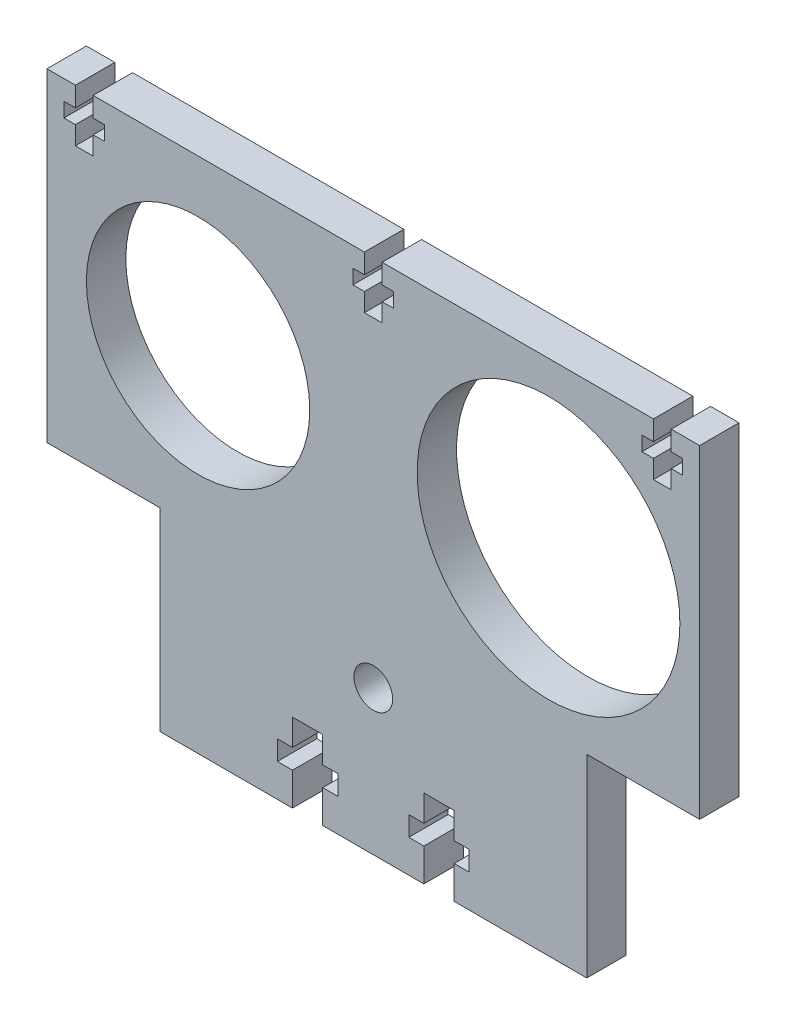
SolidWorks part; units mm, degrees
material "ABS"
ref_plane "Front Plane" through (0, 0, 0) normal (0, 0, 1) x (1, 0, 0)
ref_plane "Top Plane" through (0, 0, 0) normal (0, 1, 0) x (1, 0, 0)
ref_plane "Right Plane" through (0, 0, 0) normal (1, 0, 0) x (0, 0, -1)
sketch "Sketch1" plane through (0, 0, 0) normal (0, 0, 1) x (1, 0, 0)
  line L0 (0, 0) -> (-26.6757, 31.7908) construction
  line L1 (0, 0) -> (0, 56.7908) construction
  line L2 (-32.5, 7.5) -> (-32.5, -22)
  line L3 (-32.5, -22) -> (32.5, -22)
  line L4 (32.5, 7.5) -> (49.6757, 7.5)
  line L5 (0, 0) -> (0, -22) construction
  line L6 (49.6757, 7.5) -> (49.6757, 56.7908)
  line L7 (0, 0) -> (26.6757, 31.7908) construction
  line L10 (-32.5, 7.5) -> (-49.6757, 7.5)
  line L11 (-49.6757, 7.5) -> (-49.6757, 56.7908)
  line L12 (-49.6757, 56.7908) -> (49.6757, 56.7908)
  line L13 (32.5, 7.5) -> (32.5, -22)
  circle A0 centre (0, 0) radius 2.95
  circle A1 centre (-26.6757, 31.7908) radius 17
  circle A2 centre (26.6757, 31.7908) radius 20
  point P16 (0, 56.7908)
  dimension "D1" = 5.9
  dimension "D9" = 34
  dimension "D10" = 40
  dimension "D2" = 41.5
  dimension "D4" = 40
  dimension "D5" = 22
  dimension "D6" = 65
  dimension "D7" = 29.5
  dimension "D8" = 23
  dimension "D3" = 25
  dimension "D11" = 40
extrude "Boss-Extrude1" add sketch "Sketch1" along normal blind 6
sketch "Sketch3" plane through (0, 0, 6) normal (0, 0, 1) x (1, 0, 0)
  line L0 (-32.5, -22) -> (32.5, -22) construction
  line L1 (-12.3, -22) -> (-7.7, -22)
  line L2 (-12.3, -22) -> (-12.3, -17)
  line L3 (-12.3, -10) -> (-7.7, -10)
  line L4 (-7.7, -22) -> (-7.7, -17)
  line L5 (0, 0) -> (0, -22) construction
  line L6 (-7.7, -14) -> (-5.4, -14)
  line L7 (-14.6, -14) -> (-12.3, -14)
  line L8 (-14.6, -14) -> (-14.6, -17)
  line L9 (-14.6, -17) -> (-12.3, -17)
  line L10 (-5.4, -14) -> (-5.4, -17)
  line L11 (-12.3, -14) -> (-12.3, -10)
  line L12 (-7.7, -17) -> (-5.4, -17)
  line L13 (-7.7, -14) -> (-7.7, -10)
  line L14 (7.7, -14) -> (7.7, -10)
  line L15 (7.7, -17) -> (5.4, -17)
  line L16 (12.3, -14) -> (12.3, -10)
  line L17 (5.4, -14) -> (5.4, -17)
  line L18 (14.6, -17) -> (12.3, -17)
  line L19 (14.6, -14) -> (14.6, -17)
  line L20 (14.6, -14) -> (12.3, -14)
  line L21 (7.7, -14) -> (5.4, -14)
  line L22 (7.7, -22) -> (7.7, -17)
  line L23 (12.3, -10) -> (7.7, -10)
  line L24 (12.3, -22) -> (12.3, -17)
  line L25 (12.3, -22) -> (7.7, -22)
  point P6 (-10, -10)
  point P18 (-13.45, -17)
  dimension "D1" = 4.6
  dimension "D2" = 10
  dimension "D3" = 12
  dimension "D4" = 9.2
  dimension "D5" = 3
  dimension "D6" = 5
extrude "Cut-Extrude2" cut sketch "Sketch3" against normal through all
sketch "Sketch4" plane through (0, 0, 6) normal (0, 0, 1) x (1, 0, 0)
  line L0 (42.65, 56.7908) -> (42.65, 53.7908)
  line L1 (49.6757, 56.7908) -> (-49.6757, 56.7908) construction
  line L2 (42.65, 53.7908) -> (40.9, 53.7908)
  line L3 (40.9, 53.7908) -> (40.9, 51.5908)
  line L4 (40.9, 51.5908) -> (42.65, 51.5908)
  line L5 (42.65, 51.5908) -> (42.65, 48.7908)
  line L6 (42.65, 48.7908) -> (45.35, 48.7908)
  line L7 (45.35, 48.7908) -> (45.35, 51.5908)
  line L8 (45.35, 51.5908) -> (47.1, 51.5908)
  line L9 (47.1, 51.5908) -> (47.1, 53.7908)
  line L10 (47.1, 53.7908) -> (45.35, 53.7908)
  line L11 (45.35, 53.7908) -> (45.35, 56.7908)
  line L12 (45.35, 56.7908) -> (42.65, 56.7908)
  line L13 (0, 0) -> (0, 56.7908) construction
  line L14 (-45.35, 56.7908) -> (-42.65, 56.7908)
  line L15 (-45.35, 53.7908) -> (-45.35, 56.7908)
  line L16 (-47.1, 53.7908) -> (-45.35, 53.7908)
  line L17 (-47.1, 51.5908) -> (-47.1, 53.7908)
  line L18 (-45.35, 51.5908) -> (-47.1, 51.5908)
  line L19 (-45.35, 48.7908) -> (-45.35, 51.5908)
  line L20 (-42.65, 48.7908) -> (-45.35, 48.7908)
  line L21 (-42.65, 51.5908) -> (-42.65, 48.7908)
  line L22 (-40.9, 51.5908) -> (-42.65, 51.5908)
  line L23 (-40.9, 53.7908) -> (-40.9, 51.5908)
  line L24 (-42.65, 53.7908) -> (-40.9, 53.7908)
  line L25 (-42.65, 56.7908) -> (-42.65, 53.7908)
  line L26 (-1.35, 56.7908) -> (1.35, 56.7908)
  line L27 (1.35, 56.7908) -> (1.35, 53.7908)
  line L28 (1.35, 53.7908) -> (3.1, 53.7908)
  line L29 (3.1, 53.7908) -> (3.1, 51.5908)
  line L30 (3.1, 51.5908) -> (1.35, 51.5908)
  line L31 (1.35, 51.5908) -> (1.35, 48.7908)
  line L32 (1.35, 48.7908) -> (-1.35, 48.7908)
  line L33 (-1.35, 48.7908) -> (-1.35, 51.5908)
  line L34 (-1.35, 51.5908) -> (-3.1, 51.5908)
  line L35 (-3.1, 51.5908) -> (-3.1, 53.7908)
  line L36 (-3.1, 53.7908) -> (-1.35, 53.7908)
  line L37 (-1.35, 53.7908) -> (-1.35, 56.7908)
  point P18 (44, 48.7908)
  point P39 (0, 0)
  point P44 (6.3485, 42.7357)
  point P45 (4.4469, 41.7444)
  point P46 (0, 48.7908)
  point P47 (9.3855, 51.2793)
  point P48 (0, 0)
  point P49 (0, 0)
  dimension "D1" = 2.7
  dimension "D2" = 2.2
  dimension "D3" = 6.2
  dimension "D4" = 3
  dimension "D5" = 8
  dimension "D6" = 44
extrude "Cut-Extrude3" cut sketch "Sketch4" against normal through all
equation "\"smallPulleyTeeth\"= 30"
equation "\"largePulleyTeeth\"= 30"
equation "\"eighthThick\"= 3.0mm"
equation "\"sixteenthThick\" = 1.7mm"
equation "\"quarterThick\"=6.0mm"
equation "\"OD\" = 145mm"
equation "\"puckAngle\" = 60.5deg"
equation "\"puckDiam\" = 76.5mm"
equation "\"axlePress\" = 5.9mm"
equation "\"D1@Sketch1\"=\"axlePress\""
equation "\"D1@Boss-Extrude1\"=\"quarterThick\""
equation "\"press\" = 0.2mm"
equation "\"wheelClear\" = 0.3mm"
equation "\"10-32clear\" = 4.8mm"
equation "\"D1@Sketch3\"=\"10-32clear\" - \"press\""
equation "\"6-32clear\" = 3.3mm"
equation "\"8-32clear\" = 4.0mm"
equation "\"wheelHeight\" = 22mm"
equation "\"D5@Sketch1\"=\"wheelHeight\""
equation "\"4-40clear\" = 3.0mm"
equation "\"wheelWell\" = 65mm"
equation "\"D6@Sketch1\"=\"wheelWell\""
equation "\"D7@Sketch1\"=\"eighthThick\"*10 - 0.5"
equation "\"puckDist\" = 85mm"
equation "\"scoopFillet\" = 5mm"
equation "\"10-32tap\" = 4.45mm"
equation "\"ledSmall\" = 3.1mm"
equation "\"ledLarge\" = 4.2mm"
equation "\"ledLength\" = 4.2mm"
equation "\"4-40close\" = 2.7mm"
equation "\"4-40nutThick\" = 2.2mm"
equation "\"4-40nutWidth\" = 6.2mm"
equation "\"D3@Sketch4\"=\"4-40nutWidth\""
equation "\"D2@Sketch4\"=\"4-40nutThick\""
equation "\"D1@Sketch4\"=\"4-40close\""
